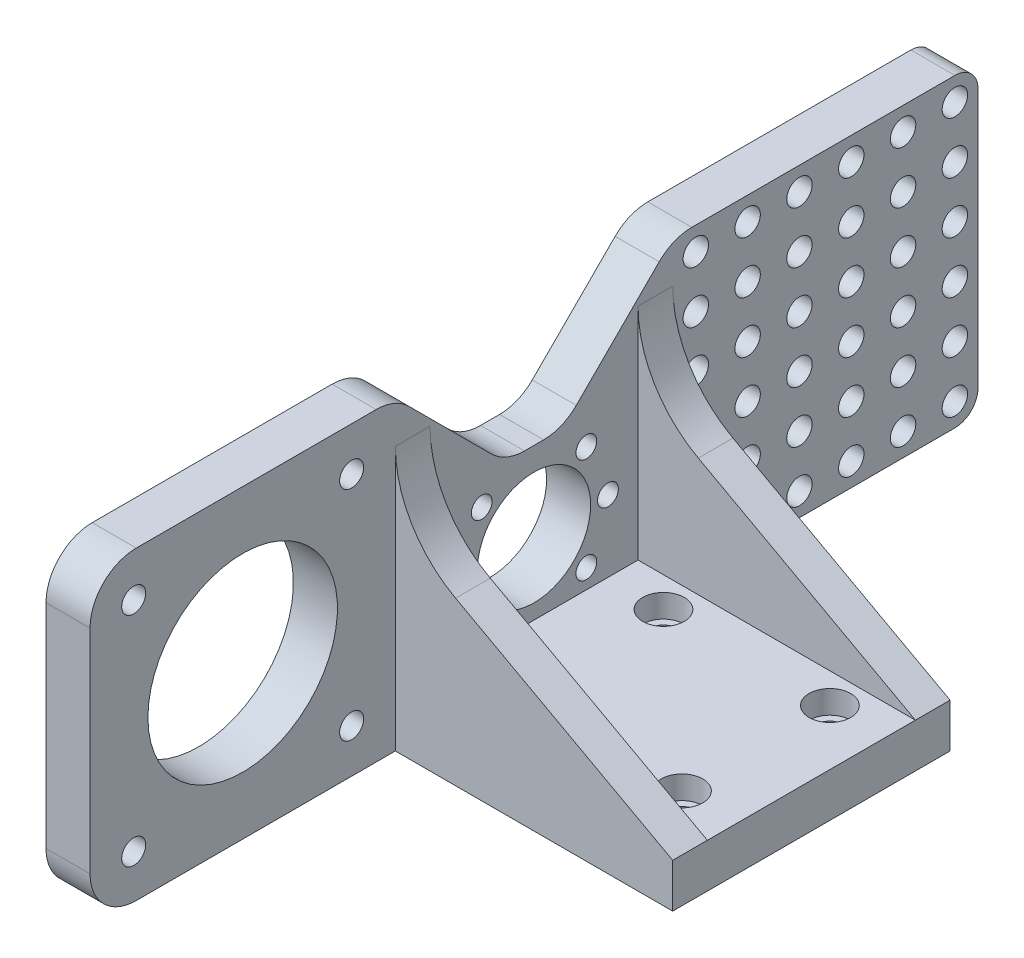
SolidWorks part; units mm, degrees
ref_plane "Front Plane" through (0, 0, 0) normal (0, 0, 1) x (1, 0, 0)
ref_plane "Top Plane" through (0, 0, 0) normal (0, 1, 0) x (1, 0, 0)
ref_plane "Right Plane" through (0, 0, 0) normal (1, 0, 0) x (0, 0, -1)
sketch "Sketch1" plane through (0, 0, 0) normal (0, 1, 0) x (1, 0, 0)
  line L0 (30, 60) -> (30, 0) construction
  line L1 (0, 0) -> (60, 0)
  line L2 (0, 0) -> (0, 60)
  line L3 (0, 60) -> (60, 60)
  line L4 (60, 0) -> (60, 60)
  line L5 (12, 46) -> (48, 46) construction
  line L6 (12, 46) -> (12, 14) construction
  line L7 (12, 14) -> (48, 14) construction
  line L8 (48, 46) -> (48, 14) construction
  line L9 (0, 30) -> (60, 30) construction
  circle A0 centre (12, 14) radius 2.95
  circle A1 centre (12, 46) radius 2.95
  circle A2 centre (48, 46) radius 2.95
  circle A3 centre (48, 14) radius 2.95
  dimension "D3" = 5.9
  dimension "D1" = 36
  dimension "D2" = 32
  dimension "D4" = 60
  dimension "D5" = 60
extrude "Boss-Extrude1" add sketch "Sketch1" along normal blind 9.525
sketch "Sketch2" plane through (0, 9.525, 0) normal (0, 1, 0) x (1, 0, 0)
  circle A0 centre (12, 14) radius 4.5
  circle A1 centre (12, 46) radius 4.5
  circle A2 centre (48, 46) radius 4.5
  circle A3 centre (48, 14) radius 4.5
  dimension "D1" = 9
extrude "Cut-Extrude1" cut sketch "Sketch2" against normal blind 5
sketch "Sketch3" plane through (0, 0, 0) normal (-1, 0, 0) x (0, 0, 1)
  line L0 (-60, 9.525) -> (0, 9.525) construction
  line L1 (-60, 0) -> (0, 0)
  line L2 (-60, 0) -> (-60, 42.25)
  line L3 (-60, 42.25) -> (0, 42.25)
  line L4 (0, 0) -> (0, 42.25)
  line L6 (0, 9.525) -> (0, 0) construction
  line L7 (-30, 44.025) -> (-30, 0) construction
  line L8 (-30, 25) -> (0, 25) construction
  line L9 (-30, 25) -> (-18.6863, 36.3137) construction
  circle A0 centre (-30, 25) radius 12.25
  circle A1 centre (-30, 25) radius 16 construction
  circle A2 centre (-18.6863, 36.3137) radius 2.25
  circle A3 centre (-14, 25) radius 2.25
  circle A4 centre (-18.6863, 13.6863) radius 2.25
  circle A5 centre (-41.3137, 13.6863) radius 2.25
  circle A6 centre (-46, 25) radius 2.25
  circle A7 centre (-41.3137, 36.3137) radius 2.25
  point P14 (-30, 42.25)
  dimension "D1" = 24.5
  dimension "D2" = 15.475
  dimension "D3" = 5
  dimension "D4" = 32
  dimension "D6" = 4.5
  dimension "D5" = 45
  dimension "D7" = 3
extrude "Boss-Extrude2" add sketch "Sketch3" along normal blind 9.525
sketch "Sketch4" plane through (-9.525, 0, 0) normal (-1, 0, 0) x (0, 0, 1)
  line L0 (33.02, 72.7999) -> (33.02, 6.7599) construction
  line L1 (0, 0) -> (66.04, 0)
  line L2 (0, 0) -> (0, 66.04)
  line L3 (0, 66.04) -> (66.04, 66.04)
  line L4 (66.04, 0) -> (66.04, 66.04)
  line L5 (9.45, 56.59) -> (56.59, 56.59) construction
  line L6 (9.45, 56.59) -> (9.45, 9.45) construction
  line L7 (9.45, 9.45) -> (56.59, 9.45) construction
  line L8 (56.59, 56.59) -> (56.59, 9.45) construction
  line L9 (46.2537, 33.02) -> (-19.7863, 33.02) construction
  line L11 (0, 0) -> (0, 42.25) construction
  line L14 (-60, 0) -> (0, 0) construction
  line L15 (-30, 98.1688) -> (-30, 122.9789) construction
  line L16 (-60, 66.04) -> (-126.04, 66.04)
  line L17 (-126.04, 0) -> (-126.04, 66.04)
  line L18 (-60, 0) -> (-126.04, 0)
  line L19 (-60, 0) -> (-60, 66.04)
  circle A0 centre (56.59, 56.59) radius 2.6
  circle A1 centre (9.45, 56.59) radius 2.6
  circle A2 centre (9.45, 9.45) radius 2.6
  circle A3 centre (56.59, 9.45) radius 2.6
  circle A4 centre (33.02, 33.02) radius 20.5
  circle A6 centre (-30, 25) radius 12.25 construction
  circle A7 centre (-121.04, 61.04) radius 2.75
  circle A8 centre (-109.832, 61.04) radius 2.75
  circle A9 centre (-98.624, 61.04) radius 2.75
  circle A10 centre (-87.416, 61.04) radius 2.75
  circle A11 centre (-76.208, 61.04) radius 2.75
  circle A12 centre (-65, 61.04) radius 2.75
  circle A13 centre (-109.832, 49.832) radius 2.75
  circle A14 centre (-98.624, 49.832) radius 2.75
  circle A15 centre (-87.416, 49.832) radius 2.75
  circle A16 centre (-76.208, 49.832) radius 2.75
  circle A17 centre (-65, 49.832) radius 2.75
  circle A18 centre (-109.832, 38.624) radius 2.75
  circle A19 centre (-98.624, 38.624) radius 2.75
  circle A20 centre (-87.416, 38.624) radius 2.75
  circle A21 centre (-76.208, 38.624) radius 2.75
  circle A22 centre (-65, 38.624) radius 2.75
  circle A23 centre (-109.832, 27.416) radius 2.75
  circle A24 centre (-98.624, 27.416) radius 2.75
  circle A25 centre (-87.416, 27.416) radius 2.75
  circle A26 centre (-76.208, 27.416) radius 2.75
  circle A27 centre (-65, 27.416) radius 2.75
  circle A28 centre (-109.832, 16.208) radius 2.75
  circle A29 centre (-98.624, 16.208) radius 2.75
  circle A30 centre (-87.416, 16.208) radius 2.75
  circle A31 centre (-76.208, 16.208) radius 2.75
  circle A32 centre (-65, 16.208) radius 2.75
  circle A33 centre (-109.832, 5) radius 2.75
  circle A34 centre (-98.624, 5) radius 2.75
  circle A35 centre (-87.416, 5) radius 2.75
  circle A36 centre (-76.208, 5) radius 2.75
  circle A37 centre (-65, 5) radius 2.75
  circle A38 centre (-121.04, 49.832) radius 2.75
  circle A39 centre (-121.04, 38.624) radius 2.75
  circle A40 centre (-121.04, 27.416) radius 2.75
  circle A41 centre (-121.04, 16.208) radius 2.75
  circle A42 centre (-121.04, 5) radius 2.75
  point P17 (66.04, 33.02)
  point P18 (33.02, 66.04)
  point P28 (-30, 25)
  dimension "D3" = 5.2
  dimension "D5" = 41
  dimension "D6" = 5.5
  dimension "D1" = 66.04
  dimension "D2" = 66.04
  dimension "D4" = 47.14
  dimension "D7" = 5
  dimension "D8" = 5
  dimension "D11" = 5
  dimension "D12" = 5
  dimension "D9" = 6
  dimension "D10" = 6
extrude "Boss-Extrude3" add sketch "Sketch4" against normal blind 9.525
sketch "Sketch5" plane through (0, 0, 0) normal (0, 0, 1) x (1, 0, 0)
  line L0 (60, 9.525) -> (0, 42.25)
  line L1 (0, 9.525) -> (60, 9.525) construction
  line L2 (0, 0) -> (0, 66.04) construction
  line L3 (0, 42.25) -> (0, 9.525)
  line L4 (0, 9.525) -> (60, 9.525)
  dimension "D1" = 60
  dimension "D2" = 32.725
extrude "Boss-Extrude4" add sketch "Sketch5" against normal blind 7.5
ref_plane "Plane1" through (0, 0, -30) normal (0, 0, 1) x (1, 0, 0)
mirror "Mirror1" about plane through (0, 0, -30) normal (0, 0, 1) of "Boss-Extrude4"
chamfer "Chamfer1" distance 23.79 angle 45 2 edges at (-4.7625, 42.25, -60) (-4.7625, 42.25, 0)
fillet "Fillet1" radius 10 6 edges at (-4.7625, 42.25, -36.21) (-4.7625, 42.25, -23.79) (-4.7625, 0, 66.04) (-4.7625, 66.04, 66.04) (-4.7625, 66.04, -60) (-4.7625, 66.04, 0)
fillet "Fillet2" radius 5 2 edges at (-4.7625, 0, -126.04) (-4.7625, 66.04, -126.04)
fillet "Fillet3" radius 25 2 edges at (0, 42.25, -56.25) (0, 42.25, -3.75)
sketch "Sketch7" plane through (-9.525, 0, 0) normal (-1, 0, 0) x (0, 0, 1)
  line L0 (-121.04, 61.04) -> (-65, 5) construction
  circle A0 centre (33.02, 33.02) radius 20.5 construction
  circle A1 centre (33.02, 33.02) radius 20.5
  circle A2 centre (-121.04, 61.04) radius 2.75 construction
  circle A3 centre (-65, 5) radius 2.75 construction
  circle A4 centre (-121.04, 61.04) radius 2.75
  circle A5 centre (-65, 5) radius 2.75
  point P9 (-93.02, 33.02)
